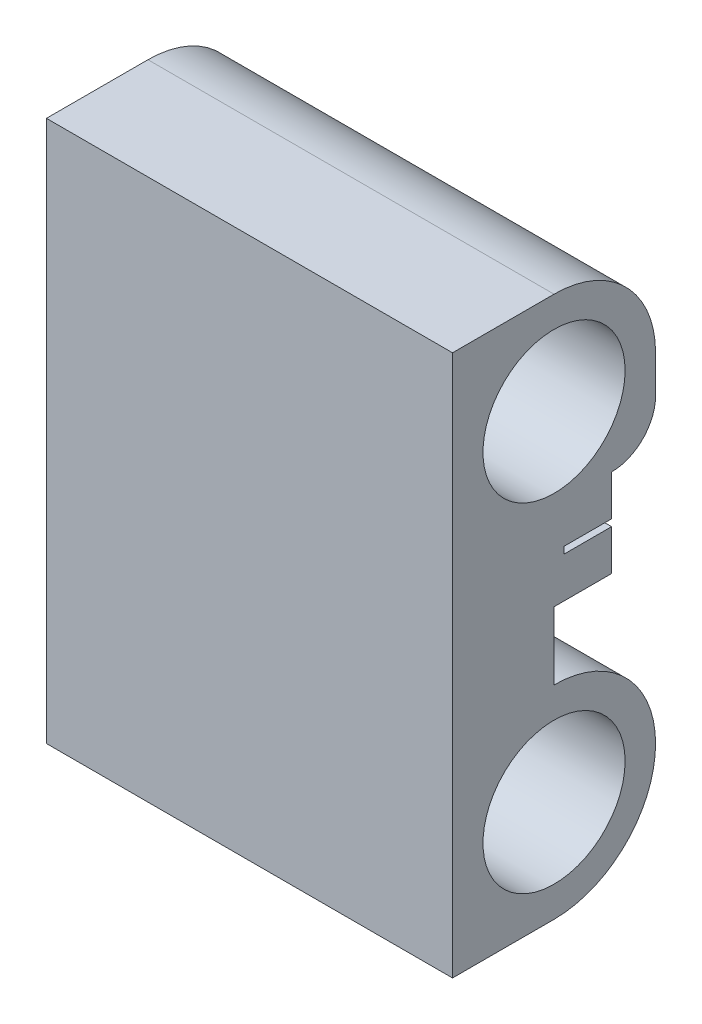
SolidWorks part; units mm, degrees
ref_plane "Спереди" through (0, 0, 0) normal (0, 0, 1) x (1, 0, 0)
ref_plane "Сверху" through (0, 0, 0) normal (0, 1, 0) x (1, 0, 0)
ref_plane "Справа" through (0, 0, 0) normal (1, 0, 0) x (0, 0, -1)
sketch "Эскиз1" plane through (0, 0, 0) normal (1, 0, 0) x (0, 0, -1)
  line L0 (0, 0) -> (0, 80)
  line L1 (0, 80) -> (30, 80)
  line L2 (30, 80) -> (30, 53)
  line L3 (23.5, 40) -> (15, 40)
  line L4 (15, 40) -> (15, 30)
  line L5 (15, 30) -> (30, 30)
  line L6 (30, 30) -> (30, 0)
  line L7 (30, 0) -> (0, 0)
  line L8 (15, 65) -> (15, 15) construction
  line L9 (23.5, 46) -> (16.5, 46)
  line L10 (16.5, 46) -> (16.5, 47)
  line L11 (16.5, 47) -> (23.5, 47)
  line L12 (23.5, 46) -> (23.5, 40)
  line L13 (30, 53) -> (23.5, 53)
  line L14 (23.5, 53) -> (23.5, 47)
  circle A0 centre (15, 15) radius 10.5
  circle A1 centre (15, 65) radius 10.5
  point P13 (0, 40)
  dimension "D4" = 21
  dimension "D6" = 21
  dimension "D1" = 1
  dimension "D2" = 15
  dimension "D3" = 15
  dimension "D5" = 30
  dimension "D7" = 15
  dimension "D8" = 50
  dimension "D9" = 15
  dimension "D10" = 7
  dimension "D11" = 6
  dimension "D12" = 1.5
  dimension "D13" = 15
  dimension "D14" = 6
  dimension "D15" = 8.5
extrude "Бобышка-Вытянуть2" add sketch "Эскиз1" along normal blind 60
fillet "Скругление1" radius 15 1 edges at (30, 30, -30)
fillet "Скругление5" radius 15 1 edges at (30, 80, -30)
fillet "Скругление3" radius 15 1 edges at (30, 0, -30)
fillet "Скругление9" radius 6.5 1 edges at (30, 53, -30)
